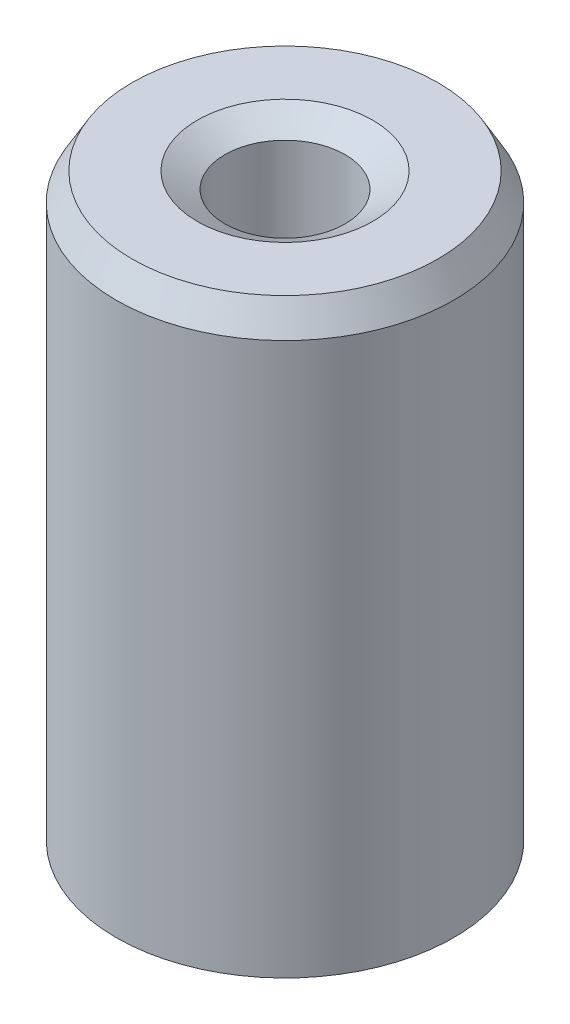
SolidWorks part; units mm, degrees
ref_plane "Front Plane" through (0, 0, 0) normal (0, 0, 1) x (1, 0, 0)
ref_plane "Top Plane" through (0, 0, 0) normal (0, 1, 0) x (1, 0, 0)
ref_plane "Right Plane" through (0, 0, 0) normal (1, 0, 0) x (0, 0, -1)
sketch "Sketch1" plane through (0, 0, 0) normal (0, 1, 0) x (1, 0, 0)
  circle A0 centre (0, 0) radius 7.5
  dimension "SLEEVE_OD" = 15
extrude "Boss-Extrude1" add sketch "Sketch1" along normal blind 26.4625
sketch "Sketch2" plane through (0, 0, 0) normal (0, 1, 0) x (1, 0, 0)
  circle A0 centre (0, 0) radius 2.6694
  dimension "BORE_D" = 5.3388
extrude "Cut-Extrude1" cut sketch "Sketch2" along normal through all
chamfer "Chamfer1" distance 1.2288 angle 30 4 edges at (0, 26.4625, 2.6694) (0, 0, 2.6694) (0, 0, 7.5) (0, 26.4625, 7.5) first distance on face at (0, 26.4625, 2.6694) first distance on face at (0, 0, 2.6694) first distance on face at (0, 26.4625, 7.5)
